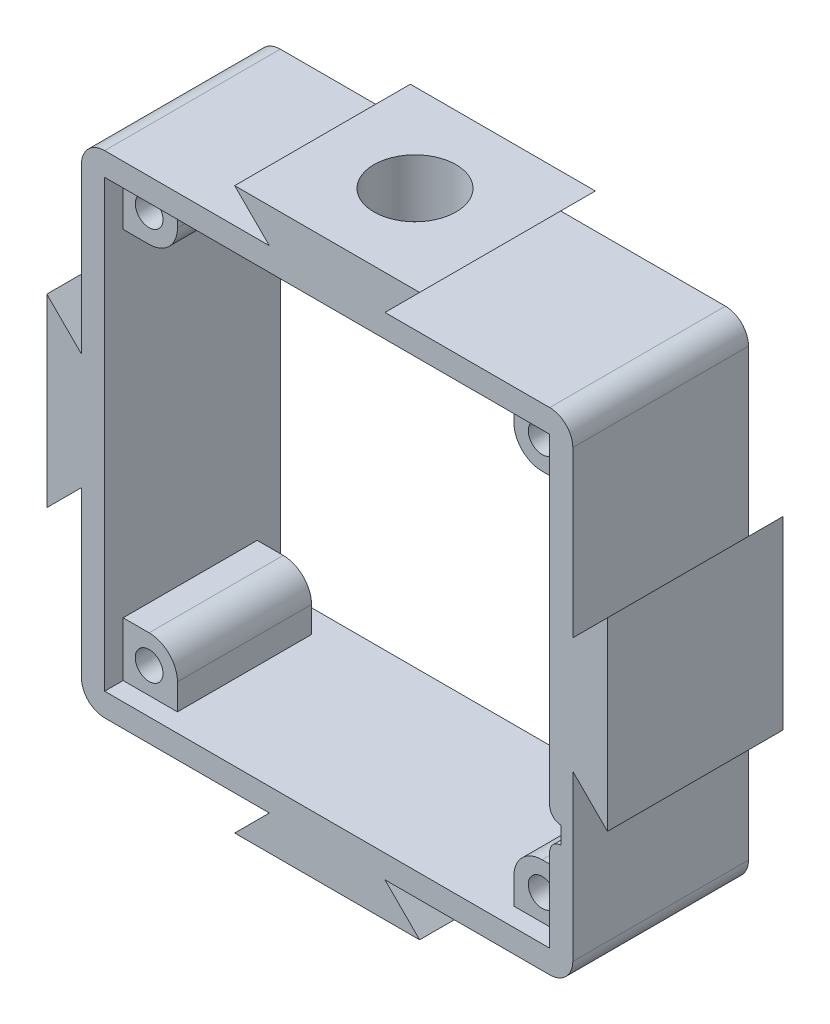
SolidWorks part; units mm, degrees
ref_plane "Front Plane" through (0, 0, 0) normal (0, 0, 1) x (1, 0, 0)
ref_plane "Top Plane" through (0, 0, 0) normal (0, 1, 0) x (1, 0, 0)
ref_plane "Right Plane" through (0, 0, 0) normal (1, 0, 0) x (0, 0, -1)
sketch "Sketch1" plane through (0, 0, 0) normal (0, 0, 1) x (1, 0, 0)
  line L0 (19.05, -19.05) -> (19.05, 19.05) construction
  line L5 (21.25, 21.25) -> (-21.25, 21.25)
  line L6 (-21.25, 21.25) -> (-21.25, -21.25)
  line L7 (-19.05, -19.05) -> (19.05, -19.05) construction
  line L8 (-19.05, 19.05) -> (-19.05, -19.05) construction
  line L9 (19.05, 19.05) -> (-19.05, 19.05) construction
  line L10 (19.05, -19.05) -> (19.05, 19.05) construction
  line L11 (-19.05, -19.05) -> (19.05, -19.05) construction
  line L12 (-19.05, 19.05) -> (-19.05, -19.05) construction
  line L13 (19.05, 19.05) -> (-19.05, 19.05) construction
  line L14 (19.25, -19.25) -> (19.25, 19.25)
  line L15 (19.25, 19.25) -> (-19.25, 19.25)
  line L16 (-19.25, 19.25) -> (-19.25, -19.25)
  line L17 (-19.25, -19.25) -> (19.25, -19.25)
  line L18 (-21.25, -21.25) -> (21.25, -21.25)
  line L19 (21.25, -21.25) -> (21.25, 21.25)
  dimension "D2" = 2
  dimension "D1" = 0.2
extrude "Boss-Extrude2" add sketch "Sketch1" against normal up to surface (15.2 mm away)
sketch "Sketch2" plane through (0, 0, -1.6) normal (0, 0, -1) x (-1, 0, 0)
  line L0 (17, -14.55) -> (19.25, -14.55)
  line L1 (19.25, 19.25) -> (19.25, -19.25) construction
  line L2 (14.55, -17) -> (14.55, -19.25)
  line L3 (19.25, -19.25) -> (-19.25, -19.25) construction
  line L4 (19.25, -19.25) -> (14.55, -19.25)
  line L5 (19.25, -14.55) -> (19.25, -19.25)
  line L6 (19.05, -19.05) -> (-19.05, -19.05) construction
  line L7 (0, 0) -> (-50000, 0) construction
  line L8 (0, 0) -> (0, 50000) construction
  line L9 (19.25, 14.55) -> (19.25, 19.25)
  line L10 (19.25, 19.25) -> (14.55, 19.25)
  line L11 (14.55, 17) -> (14.55, 19.25)
  line L12 (17, 14.55) -> (19.25, 14.55)
  line L13 (-19.25, -14.55) -> (-19.25, -19.25)
  line L14 (-19.25, -19.25) -> (-14.55, -19.25)
  line L15 (-14.55, -17) -> (-14.55, -19.25)
  line L16 (-17, -14.55) -> (-19.25, -14.55)
  line L17 (-17, 14.55) -> (-19.25, 14.55)
  line L18 (-14.55, 17) -> (-14.55, 19.25)
  line L19 (-19.25, 19.25) -> (-14.55, 19.25)
  line L20 (-19.25, 14.55) -> (-19.25, 19.25)
  circle A2 centre (17, -17) radius 1.2 construction
  circle A3 centre (17, -17) radius 1.2
  arc A4 (17, -14.55) -> (14.55, -17) centre (17, -17) ccw
  arc A5 (17, 14.55) -> (14.55, 17) centre (17, 17) cw
  circle A6 centre (17, 17) radius 1.2
  arc A7 (-17, -14.55) -> (-14.55, -17) centre (-17, -17) cw
  circle A8 centre (-17, -17) radius 1.2
  circle A9 centre (-17, 17) radius 1.2
  arc A10 (-17, 14.55) -> (-14.55, 17) centre (-17, 17) ccw
  dimension "D1" = 4.5
extrude "Boss-Extrude4" add sketch "Sketch2" along normal offset from surface (11.6 mm away) 0.4 up to face at (0, 0, 0)
sketch "Sketch5" plane through (0, 0, 0) normal (0, 0, 1) x (1, 0, 0)
  line L0 (-21.25, 5) -> (-21.25, -5)
  line L1 (-21.25, 21.25) -> (-21.25, -21.25) construction
  line L2 (-21.25, -5) -> (-24.25, -8)
  line L3 (-24.25, -8) -> (-24.25, 8)
  line L4 (-24.25, 8) -> (-21.25, 5)
  point P5 (-24.25, 0)
  dimension "D1" = 45
  dimension "D2" = 45
  dimension "D3" = 10
  dimension "D4" = 3
extrude "Boss-Extrude5" add sketch "Sketch5" against normal up to surface (15.2 mm away) up to face at (0, 0, -15.2)
ref_axis "Axis1" through (0, 0, 0) along (0, 0, 1)
pattern_circular "CirPattern1" count 4 every 90 about axis through (0, 0, 0) along (0, 0, 1) of "Boss-Extrude5"
sketch "Sketch3" plane through (0, 0, 0) normal (0, 0, 1) x (1, 0, 0)
  line L0 (20.25, -11.05) -> (20.25, -9.55) construction
  line L1 (20.25, -11.05) -> (20.25, -9.55)
  line L2 (19.25, -8.55) -> (19.25, -12.05)
  arc A0 (19.25, -8.55) -> (20.25, -9.55) centre (20.25, -8.55) ccw construction
  arc A1 (20.25, -11.05) -> (19.25, -12.05) centre (20.25, -12.05) ccw construction
  arc A2 (19.25, -8.55) -> (20.25, -9.55) centre (20.25, -8.55) ccw
  arc A3 (20.25, -11.05) -> (19.25, -12.05) centre (20.25, -12.05) ccw
extrude "Cut-Extrude2" cut sketch "Sketch3" against normal blind 4
sketch "Sketch4" plane through (0, 24.25, 0) normal (0, 1, 0) x (1, 0, 0)
  line L1 (21.25, 0) -> (-21.25, 0) construction
  line L2 (21.25, 0) -> (21.25, 15.2) construction
  line L3 (21.25, 15.2) -> (-21.25, 15.2) construction
  line L4 (-21.25, 0) -> (-21.25, 15.2) construction
  line L5 (0, 15.2) -> (0, 0) construction
  line L6 (21.25, 7.6) -> (-21.25, 7.6) construction
  line L7 (21.25, 15.2) -> (5, 15.2) construction
  line L8 (21.25, 15.2) -> (21.25, 0) construction
  circle A0 centre (0, 7.6) radius 3.55
  point P102 (0, 7.6)
  dimension "D1" = 7.1
extrude "Cut-Extrude3" cut sketch "Sketch4" against normal up to next
fillet "Fillet1" radius 2 4 edges at (21.25, 21.25, -7.6) (21.25, -21.25, -7.6) (-21.25, -21.25, -7.6) (-21.25, 21.25, -7.6)
